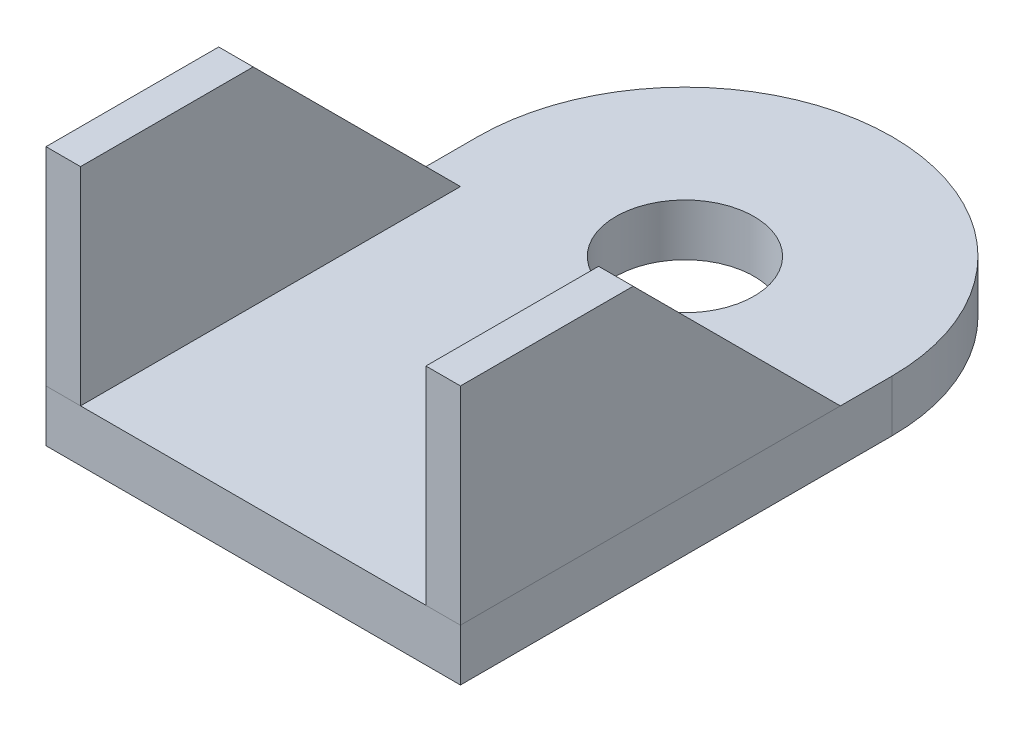
SolidWorks part; units mm, degrees
material "AISI 4130 Steel, normalized at 870C"
ref_plane "前视基准面" through (0, 0, 0) normal (0, 0, 1) x (1, 0, 0)
ref_plane "上视基准面" through (0, 0, 0) normal (0, 1, 0) x (1, 0, 0)
ref_plane "右视基准面" through (0, 0, 0) normal (1, 0, 0) x (0, 0, -1)
sketch "草图1" plane through (0, 0, 0) normal (0, 1, 0) x (1, 0, 0)
  line L0 (-12, 0) -> (-12, -25)
  line L1 (-12, -25) -> (12, -25)
  line L2 (12, -25) -> (12, 0)
  circle A0 centre (0, 0) radius 4
  circle A1 centre (0, 0) radius 12
  dimension "D1" = 8
  dimension "D2" = 24
  dimension "D3" = 25
extrude "凸台-拉伸1" add sketch "草图1" along normal blind 3 contours A1 A0 | A1 L0 L1 L2 region at (0, 0, 16.9821) region at (0, 0, -11.6606)
sketch "草图3" plane through (12, 0, 0) normal (1, 0, 0) x (0, 0, -1)
  line L0 (-25, 3) -> (-25, 15)
  line L1 (-25, 15) -> (-15, 15)
  line L2 (-15, 15) -> (-3, 3)
  line L4 (-25, 3) -> (0, 3) construction
  line L5 (-3, 3) -> (-25, 3)
  dimension "D1" = 10
  dimension "D4" = 12
extrude "凸台-拉伸2" add sketch "草图3" against normal blind 2 separate body
ref_plane "基准面1" through (0, 0, 0) normal (0, 0, 1) x (1, 0, 0)
sketch "草图4" [suppressed] plane through (0, 0, 0) normal (0, 0, 1) x (1, 0, 0)
  circle A0 centre (0, 0) radius 41.9162
sketch "草图7" plane through (0, 0, 0) normal (0, -1, 0) x (1, 0, 0)
  circle A0 centre (0, 0) radius 9
split line "分割线1"
sketch "草图8" plane through (0, 0, 0) normal (0, -1, 0) x (1, 0, 0)
  circle A0 centre (0, 0) radius 12
split line "分割线2"
extrude "Boss-Extrude1" add sketch "草图3<2>" along normal blind 2 from surface separate body starting at face at (-12, 1.5, 12.5)
sketch "草图3<2>" plane through (12, 0, 0) normal (1, 0, 0) x (0, 0, -1) same geometry as "草图3"
